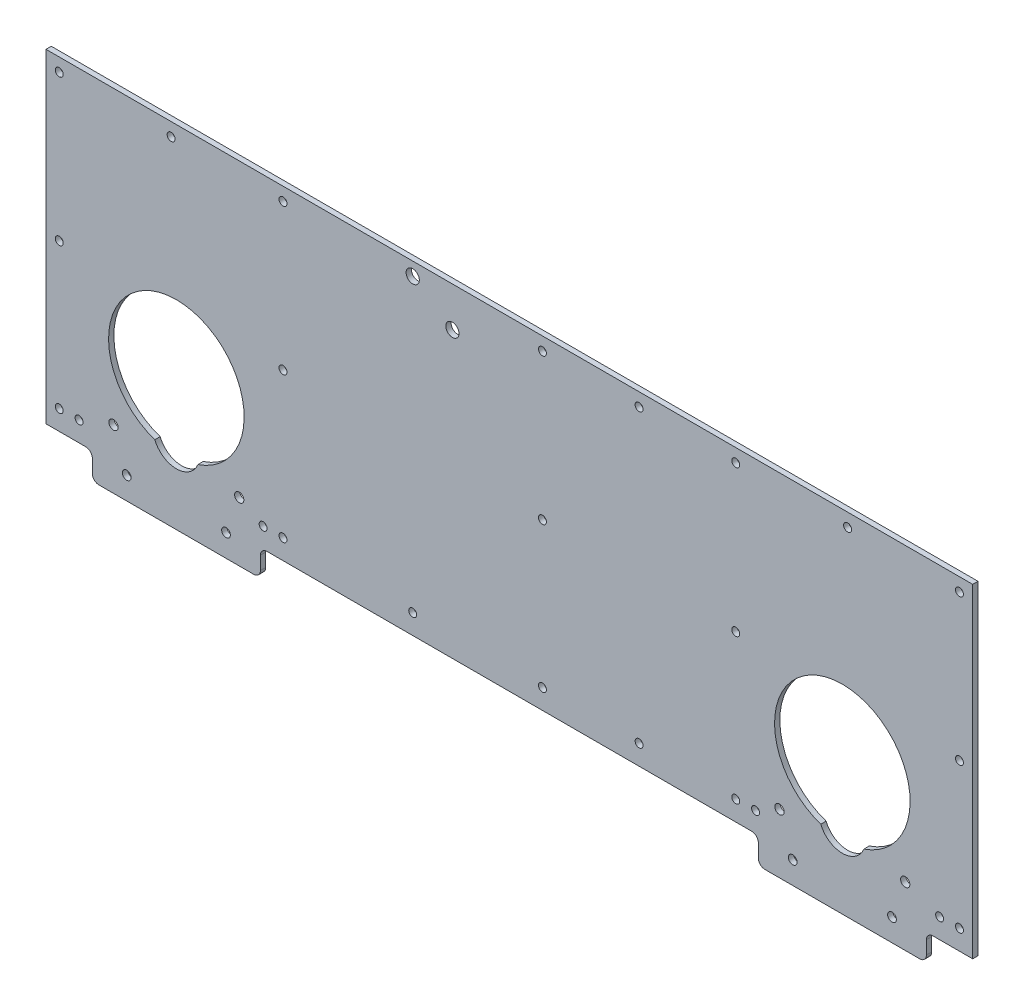
SolidWorks part; units mm, degrees
material "1345 Alloy"
ref_plane "Front Plane" through (0, 0, 0) normal (0, 0, 1) x (1, 0, 0)
ref_plane "Top Plane" through (0, 0, 0) normal (0, 1, 0) x (1, 0, 0)
ref_plane "Right Plane" through (0, 0, 0) normal (1, 0, 0) x (0, 0, -1)
sketch "Sketch1" plane through (0, 0, 0) normal (0, 0, 1) x (1, 0, 0)
  line L1 (-350, 122.5) -> (350, 122.5)
  line L2 (-350, 122.5) -> (-350, -122.5)
  line L4 (350, 122.5) -> (350, -122.5)
  line L5 (-350, 122.5) -> (350, -122.5) construction
  line L6 (-350, -122.5) -> (350, 122.5) construction
  line L9 (-350, -122.5) -> (-320, -122.5)
  line L10 (-315, -127.5) -> (-315, -137.5)
  line L11 (350, -122.5) -> (320, -122.5)
  line L12 (315, -127.5) -> (315, -137.5)
  line L13 (-188.06, -127.5) -> (-188.06, -137.5)
  line L15 (-183.06, -122.5) -> (183.06, -122.5)
  line L16 (188.06, -127.5) -> (188.06, -137.5)
  line L17 (193.06, -142.5) -> (310, -142.5)
  line L18 (-310, -142.5) -> (-193.06, -142.5)
  line L20 (-289.0304, -142.5) -> (-310, -142.5) construction
  arc A0 (320, -122.5) -> (315, -127.5) centre (320, -127.5) ccw
  arc A1 (310, -142.5) -> (315, -137.5) centre (310, -137.5) ccw
  arc A2 (-310, -142.5) -> (-315, -137.5) centre (-310, -137.5) cw
  arc A3 (-315, -127.5) -> (-320, -122.5) centre (-320, -127.5) ccw
  arc A4 (193.06, -142.5) -> (188.06, -137.5) centre (193.06, -137.5) cw
  arc A5 (188.06, -127.5) -> (183.06, -122.5) centre (183.06, -127.5) ccw
  arc A6 (-183.06, -122.5) -> (-188.06, -127.5) centre (-183.06, -127.5) ccw
  arc A7 (-188.06, -137.5) -> (-193.06, -142.5) centre (-193.06, -137.5) cw
  point P0 (0, 0)
  point P12 (315, -122.5)
  point P17 (-315, -142.5)
  point P20 (-315, -122.5)
  dimension "D6" = 5
  dimension "D7" = 5
  dimension "D1" = 700
  dimension "D2" = 245
  dimension "D3" = 35
  dimension "D4" = 35
  dimension "D5" = 20
  dimension "D8" = 126.94
  dimension "D9" = 126.94
extrude "Boss-Extrude1" add sketch "Sketch1" along normal blind 4
sketch "Sketch2" plane through (0, 0, 4) normal (0, 0, 1) x (1, 0, 0)
  line L4 (191.5296, -122.0468) -> (191.5296, -97.6368) construction
  line L5 (191.5296, -97.6368) -> (204.0296, -97.6368) construction
  line L6 (-251.5296, -43.2268) -> (-350, -43.2268) construction
  line L7 (-350, 122.5) -> (-350, -122.5) construction
  line L8 (-311.5296, -122.0468) -> (-311.5296, -97.6368) construction
  line L9 (-311.5296, -97.6368) -> (-299.0296, -97.6368) construction
  line L10 (350, -43.2268) -> (251.5296, -43.2268) construction
  line L11 (350, -122.5) -> (350, 122.5) construction
  line L12 (-214.0304, -125.6368) -> (-289.0304, -125.6368) construction
  arc A2 (-235.2738, -91.7776) -> (-267.7855, -91.7776) centre (-251.5296, -43.2268) ccw
  circle A3 centre (-299.0296, -97.6368) radius 3.5
  circle A4 centre (-204.0296, -97.6368) radius 3.5
  arc A5 (-267.7855, -91.7776) -> (-235.2738, -91.7776) centre (-251.5296, -85.1368) ccw
  circle A10 centre (-289.0304, -125.6368) radius 3.302
  circle A11 centre (-214.0304, -125.6368) radius 3.302
  arc A12 (267.7855, -91.7776) -> (235.2738, -91.7776) centre (251.5296, -43.2268) ccw
  circle A13 centre (204.0296, -97.6368) radius 3.5
  circle A14 centre (299.0296, -97.6368) radius 3.5
  arc A15 (235.2738, -91.7776) -> (267.7855, -91.7776) centre (251.5296, -85.1368) ccw
  circle A16 centre (214.0289, -125.6368) radius 3.302
  circle A17 centre (289.0289, -125.6368) radius 3.302
  point P0 (-251.5296, -85.6332)
  point P2 (251.5296, -85.6332)
  point P3 (-52.1358, -9.8326)
  dimension "D4" = 102.4
  dimension "D5" = 7
  dimension "D6" = 7
  dimension "D10" = 35.12
  dimension "D3" = 102.4
  dimension "D13" = 7
  dimension "D14" = 54.41
  dimension "D18" = 12.5
  dimension "D11" = 7
  dimension "D17" = 35.12
  dimension "D2" = 24.41
  dimension "D7" = 54.41
  dimension "D8" = 95
  dimension "D9" = 47.5
  dimension "D12" = 12.5
  dimension "D15" = 95
  dimension "D16" = 47.5
  dimension "D19" = 24.41
  dimension "D20" = 98.4704
  dimension "D21" = 98.4704
extrude "Cut-Extrude1" cut sketch "Sketch2" against normal through all
sketch "Sketch5" plane through (0, 0, 4) normal (0, 0, 1) x (1, 0, 0)
  line L0 (-340, 112.5) -> (-171, 112.5) construction
  line L1 (-325, -107.5) -> (-186, -107.5) construction
  line L2 (171, -107.5) -> (186, -107.5) construction
  line L3 (186, -107.5) -> (325, -107.5) construction
  line L4 (320, -122.5) -> (350, -122.5) construction
  line L5 (-350, -122.5) -> (-320, -122.5) construction
  line L6 (-340, -122.5) -> (-340, -107.5) construction
  line L7 (-350, 122.5) -> (-340, 122.5) construction
  line L8 (350, 122.5) -> (-350, 122.5) construction
  line L9 (-340, 122.5) -> (-340, 112.5) construction
  line L10 (25, 112.5) -> (171, 112.5) construction
  line L11 (-183.06, -122.5) -> (183.06, -122.5) construction
  line L12 (-73, 112.5) -> (-73, 92.5) construction
  line L13 (340, 112.5) -> (171, 112.5) construction
  line L14 (25, -107.5) -> (171, -107.5) construction
  line L15 (-340, 2.25) -> (340, 2.25) construction
  line L16 (-171, 112.5) -> (25, 112.5) construction
  line L17 (-171, -107.5) -> (25, -107.5) construction
  line L18 (-340, -107.5) -> (-325, -107.5) construction
  line L19 (-73, 92.5) -> (-43, 92.5) construction
  line L21 (-171, -107.5) -> (-186, -107.5) construction
  line L22 (171, -121.5) -> (171, -107.5) construction
  line L24 (-73, 112.5) -> (-73, 122.5) construction
  circle A0 centre (-340, -107.5) radius 3
  circle A1 centre (-340, 112.5) radius 3
  circle A22 centre (-171, 112.5) radius 3
  circle A23 centre (-171, -107.5) radius 3
  circle A24 centre (171, -107.5) radius 3
  circle A26 centre (340, 112.5) radius 3
  circle A27 centre (340, -107.5) radius 3
  circle A28 centre (171, 112.5) radius 3
  circle A31 centre (25, 112.5) radius 3
  circle A32 centre (25, -107.5) radius 3
  circle A33 centre (-255.5, 112.5) radius 3
  circle A34 centre (98, 112.5) radius 3
  circle A35 centre (255.5, 112.5) radius 3
  circle A36 centre (340, 2.25) radius 3
  circle A37 centre (171, 2) radius 3
  circle A38 centre (25, 2.25) radius 3
  circle A39 centre (-171, 2.25) radius 3
  circle A40 centre (-340, 2.25) radius 3
  circle A41 centre (-73, 112.5) radius 5
  circle A42 centre (-73, -107.5) radius 3
  circle A43 centre (-325, -107.5) radius 3
  circle A44 centre (186, -107.5) radius 3
  circle A45 centre (325, -107.5) radius 3
  circle A46 centre (-186, -107.5) radius 3
  circle A47 centre (98, -107.5) radius 3
  circle A48 centre (-43, 92.5) radius 5
  dimension "D3" = 6
  dimension "D6" = 6
  dimension "D8" = 6
  dimension "D9" = 6
  dimension "D10" = 6
  dimension "D11" = 6
  dimension "D13" = 6
  dimension "D15" = 6
  dimension "D17" = 6
  dimension "D18" = 6
  dimension "D12" = 6
  dimension "D20" = 6
  dimension "D21" = 6
  dimension "D22" = 6
  dimension "D23" = 6
  dimension "D24" = 6
  dimension "D25" = 10
  dimension "D26" = 6
  dimension "D28" = 6
  dimension "D29" = 6
  dimension "D56" = 10
  dimension "D2" = 169
  dimension "D4" = 10
  dimension "D5" = 10
  dimension "D7" = 169
  dimension "D14" = 169
  dimension "D16" = 169
  dimension "D19" = 146
  dimension "D27" = 15
  dimension "D30" = 98
  dimension "D31" = 98
  dimension "D32" = 15
  dimension "D33" = 15
  dimension "D34" = 139
  dimension "D35" = 139
  dimension "D36" = 15
  dimension "D37" = 15
  dimension "D38" = 15
  dimension "D39" = 15
  dimension "D40" = 15
  dimension "D41" = 15
  dimension "D42" = 15
  dimension "D43" = 15
  dimension "D44" = 15
  dimension "D45" = 15
  dimension "D46" = 10
  dimension "D47" = 10
  dimension "D48" = 10
  dimension "D49" = 10
  dimension "D50" = 10
  dimension "D51" = 10
  dimension "D52" = 10
  dimension "D53" = 10
  dimension "D54" = 20
  dimension "D55" = 30
extrude "Cut-Extrude2" cut sketch "Sketch5" against normal through all
